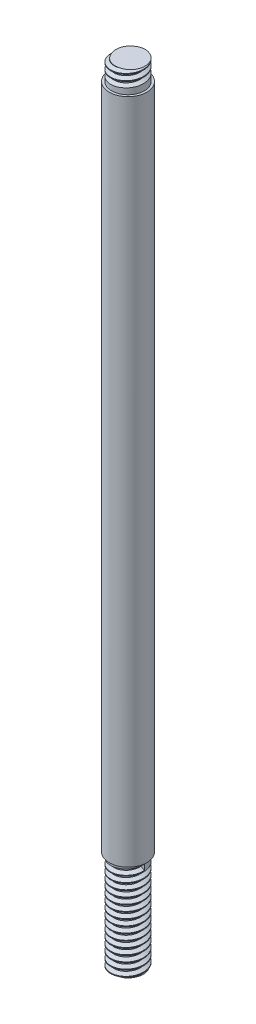
SolidWorks part; units mm, degrees
material "Alloy Steel (SS)"
ref_plane "Front Plane" through (0, 0, 0) normal (0, 0, 1) x (1, 0, 0)
ref_plane "Top Plane" through (0, 0, 0) normal (0, 1, 0) x (1, 0, 0)
ref_plane "Right Plane" through (0, 0, 0) normal (1, 0, 0) x (0, 0, -1)
sketch "Sketch1" plane through (0, 0, 0) normal (0, 1, 0) x (1, 0, 0)
  circle A0 centre (0, 0) radius 2.3813
  dimension "D1" = 4.7625
extrude "Boss-Extrude1" add sketch "Sketch1" along normal blind 100
sketch "Sketch2" plane through (0, 0, 0) normal (0, -1, 0) x (1, 0, 0)
  circle A0 centre (0, 0) radius 2.0828
  circle A1 centre (0, 0) radius 2.3813 construction
  circle A2 centre (0, 0) radius 2.3813
  dimension "D1" = 4.1656
extrude "Cut-Extrude1" cut sketch "Sketch2" against normal blind 12.7
thread "Thread1" pitch 0.7937 method cut profile "Thread Profile1" start angle 0, offset 1, length 12.7, pitch 0.7937, diameter 4.1656
ref_plane "Plane1" through (2.0828, -1, 0) normal (0, 0, 1) x (1, 0, 0)
sketch "Thread Profile1" plane through (2.0828, -1, 0) normal (0, 0, 1) x (1, 0, 0)
  line L0 (0, 0) -> (0, 0.7937) construction
  line L11 (0, 0) -> (0, 0.6945)
  line L12 (0, 0.6945) -> (-0.4296, 0.4465)
  line L13 (-0.4296, 0.4465) -> (-0.4296, 0.248)
  line L15 (-0.4296, 0.248) -> (0, 0)
  line L17 (-0.4296, 0.3473) -> (0, 0.3473) construction
  point P2 (0, 0)
  dimension "Pitch" = 0.7937
  dimension "Profile_Angle" = 60
  dimension "Profile_Land" = 0.1984
  dimension "Profile_Height" = 0.4296
sketch "Sketch3" plane through (0, 100, 0) normal (0, 1, 0) x (1, 0, 0)
  circle A0 centre (0, 0) radius 2.0856
  circle A1 centre (0, 0) radius 2.3813 construction
  circle A2 centre (0, 0) radius 2.3813
extrude "Cut-Extrude2" cut sketch "Sketch3" against normal blind 2.54
thread "Thread2" pitch 0.7937 method cut profile "Thread Profile2" start angle 0, offset 1, length 2.54, pitch 0.7937, diameter 4.1712
ref_plane "Plane2" through (-2.0856, 101, 0) normal (0, 0, 1) x (-1, 0, 0)
sketch "Thread Profile2" plane through (-2.0856, 101, 0) normal (0, 0, 1) x (-1, 0, 0)
  line L0 (0, 0) -> (0, 0.7937) construction
  line L11 (0, 0) -> (0, 0.6945)
  line L12 (0, 0.6945) -> (-0.4296, 0.4465)
  line L13 (-0.4296, 0.4465) -> (-0.4296, 0.248)
  line L15 (-0.4296, 0.248) -> (0, 0)
  line L17 (-0.4296, 0.3473) -> (0, 0.3473) construction
  point P2 (0, 0)
  dimension "Pitch" = 0.7937
  dimension "Profile_Angle" = 60
  dimension "Profile_Land" = 0.1984
  dimension "Profile_Height" = 0.4296
